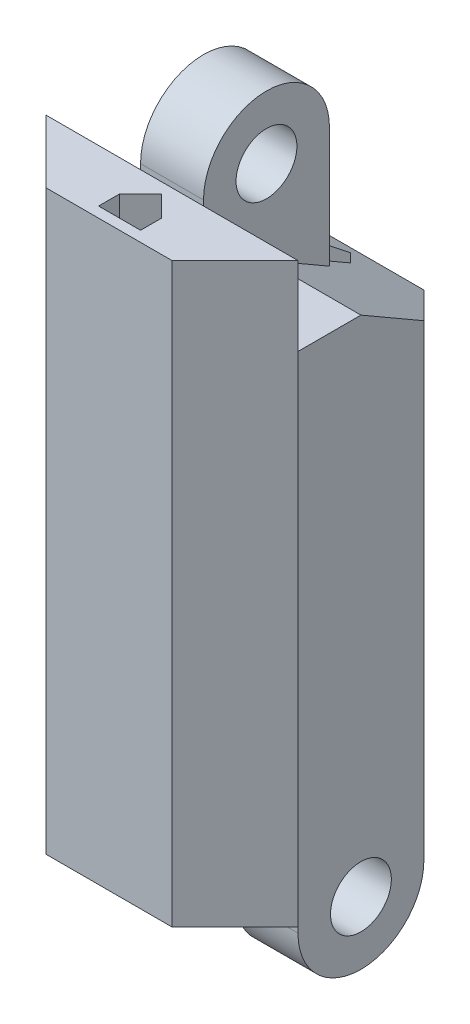
SolidWorks part; units mm, degrees
ref_plane "Front Plane" through (0, 0, 0) normal (0, 0, 1) x (1, 0, 0)
ref_plane "Top Plane" through (0, 0, 0) normal (0, 1, 0) x (1, 0, 0)
ref_plane "Right Plane" through (0, 0, 0) normal (1, 0, 0) x (0, 0, -1)
sketch "Sketch2" plane through (0, 0, 0) normal (0, 1, 0) x (1, 0, 0)
  line L0 (-3, 6) -> (3, 6)
  line L1 (3, 6) -> (6, 3)
  line L2 (6, 3) -> (6, -3)
  line L3 (6, -3) -> (3, -6)
  line L4 (3, -6) -> (-3, -6)
  line L5 (-3, -6) -> (-6, -3)
  line L6 (-6, -3) -> (-6, 3)
  line L7 (-6, 3) -> (-3, 6)
  point P2 (0, -6)
  point P9 (0, 6)
  point P12 (-6, 0)
  point P13 (6, 0)
  dimension "D1" = 12
  dimension "D2" = 12
  dimension "D3" = 6
  dimension "D4" = 6
  dimension "D5" = 6
extrude "Boss-Extrude1" add sketch "Sketch2" along normal mid plane 20 contours L7 L0 L1 L2 L3 L4 L5 L6
sketch "Sketch5" plane through (0, 0, 0) normal (1, 0, 0) x (0, 0, -1)
  line L1 (3, 10) -> (-3, 10) construction
  line L2 (0, 10) -> (6, 6.5359)
  line L3 (6, 10) -> (6, -10) construction
  line L4 (6, 6.5359) -> (6, 10)
  line L5 (6, 10) -> (0, 10)
  point P4 (0, 9.0505)
  dimension "D1" = 30
extrude "Cut-Extrude2" cut sketch "Sketch5" against normal through all both and the other way through all
mirror "Mirror3" about plane through (0, 0, 0) normal (0, 1, 0) of "Cut-Extrude2"
sketch "Sketch6" plane through (0, -10, 0) normal (0, -1, 0) x (1, 0, 0)
  line L1 (-6, 3) -> (-3, 3)
  line L2 (-6, 3) -> (-6, -3)
  line L3 (-6, -3) -> (-3, -3)
  line L4 (-3, 3) -> (-3, -3)
  dimension "D1" = 3
extrude "Boss-Extrude3" add sketch "Sketch6" along normal mid plane 8
sketch "Sketch7" plane through (0, -14, 0) normal (0, -1, 0) x (1, 0, 0)
  line L0 (-6, 3) -> (-6, -3) construction
  line L1 (-6, 0) -> (-3, 0)
  line L2 (-6, 0) -> (-6, 3)
  line L3 (-6, 3) -> (-3, 3)
  line L4 (-3, 0) -> (-3, 3)
revolve "Revolve1" add sketch "Sketch7" angle 180 about L1
sketch "Sketch8" plane through (-6, 0, 0) normal (-1, 0, 0) x (0, 0, 1)
  line L0 (-3, -14) -> (3, -14) construction
sketch "Sketch9" plane through (-6, 0, 0) normal (-1, 0, 0) x (0, 0, 1)
  line L0 (-3, -14) -> (3, -14) construction
  circle A0 centre (0, -14) radius 1.45
  dimension "D1" = 2.9
extrude "Cut-Extrude3" cut sketch "Sketch9" against normal mid plane 10
mirror "Mirror5" about plane through (0, 0, 0) normal (1, 0, 0) of "Revolve1", "Boss-Extrude3", "Cut-Extrude3"
sketch "Sketch10" plane through (0, 10, 0) normal (0, 1, 0) x (1, 0, 0)
  line L0 (-6, -3) -> (6, -3) construction
  line L1 (-1.5, -3) -> (1.5, -3)
  line L2 (-1.5, -3) -> (-1.5, 3)
  line L3 (-1.5, 3) -> (1.5, 3)
  line L4 (1.5, -3) -> (1.5, 3)
  line L5 (-1.5, -3) -> (1.5, 3) construction
  line L6 (-1.5, 3) -> (1.5, -3) construction
  point P6 (0, 0)
  dimension "D1" = 3
extrude "Boss-Extrude4" add sketch "Sketch10" along normal mid plane 8
sketch "Sketch12" plane through (0, 14, 0) normal (0, 1, 0) x (1, 0, 0)
  line L1 (-1.5, 0) -> (1.5, 0)
  line L2 (-1.5, 0) -> (-1.5, 3)
  line L3 (-1.5, 3) -> (1.5, 3)
  line L4 (1.5, 0) -> (1.5, 3)
  point P6 (0, 0)
  point P7 (-1.1195, 0.3805)
revolve "Revolve2" add sketch "Sketch12" angle 180 about L1
sketch "Sketch13" plane through (-1.5, 0, 0) normal (-1, 0, 0) x (0, 0, 1)
  line L0 (-3, 14) -> (3, 14) construction
sketch "Sketch14" plane through (-1.5, 0, 0) normal (-1, 0, 0) x (0, 0, 1)
  line L0 (-3, 14) -> (3, 14) construction
  circle A0 centre (0, 14) radius 1.45
  dimension "D1" = 2.9
extrude "Cut-Extrude4" cut sketch "Sketch14" against normal mid plane 10
sketch "Sketch17" plane through (0, 10, 0) normal (0, 1, 0) x (1, 0, 0)
  line L0 (-6, -3) -> (-1.5, -3)
  line L1 (-1.5, -3) -> (1.5, -3)
  line L2 (6, -3) -> (1.5, -3)
  line L3 (3, -6) -> (6, -3)
  line L4 (-6, -3) -> (-3, -6)
  line L5 (-3, -6) -> (3, -6)
extrude "Boss-Extrude7" add sketch "Sketch17" along normal blind 3.75
sketch "Sketch15" plane through (0, 0, 0) normal (0, 1, 0) x (1, 0, 0)
  line L0 (0, 5.5) -> (-1, 4.5)
  line L1 (-1, 4.5) -> (-1, 3.5)
  line L2 (-1, 3.5) -> (1, 3.5)
  line L3 (1, 3.5) -> (1, 4.5)
  line L4 (1, 4.5) -> (0, 5.5)
  line L6 (1, -4.5) -> (0, -3.5)
  line L7 (0, -3.5) -> (-1, -4.5)
  line L8 (-1, -4.5) -> (-1, -5.5)
  line L9 (-1, -5.5) -> (1, -5.5)
  line L10 (1, -5.5) -> (1, -4.5)
  line L12 (1.5, -3) -> (-1.5, -3) construction
  line L13 (1.5, 3) -> (-1.5, 3) construction
  dimension "D1" = 2
  dimension "D2" = 2
  dimension "D3" = 135
  dimension "D4" = 135
  dimension "D5" = 1
  dimension "D6" = 2
  dimension "D7" = 0.5
  dimension "D8" = 0.5
sketch "Sketch19" plane through (0, -10, 0) normal (0, -1, 0) x (1, 0, 0)
  line L0 (-6, 3) -> (-3, 3)
  line L1 (-3, 3) -> (3, 3)
  line L2 (3, 3) -> (6, 3)
  line L3 (6, 3) -> (3, 6)
  line L4 (3, 6) -> (-3, 6)
  line L5 (-3, 6) -> (-6, 3)
extrude "Boss-Extrude17" add sketch "Sketch19" along normal blind 3.75
extrude "Cut-Extrude6" cut sketch "Sketch15" against normal through all both and the other way through all
